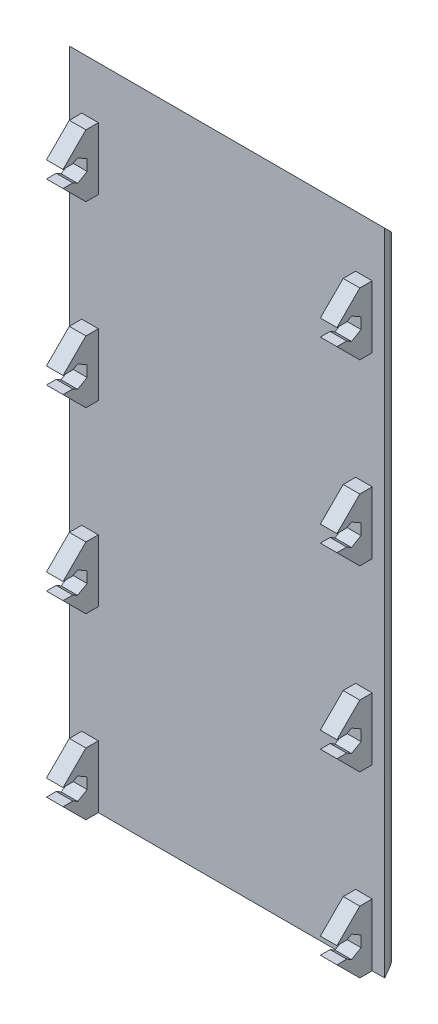
SolidWorks part; units mm, degrees
ref_plane "Front Plane" through (0, 0, 0) normal (0, 0, 1) x (1, 0, 0)
ref_plane "Top Plane" through (0, 0, 0) normal (0, 1, 0) x (1, 0, 0)
ref_plane "Right Plane" through (0, 0, 0) normal (1, 0, 0) x (0, 0, -1)
sketch "Sketch1" plane through (0, 0, 0) normal (0, 1, 0) x (1, 0, 0)
  line L0 (-9.2151, 0) -> (-9.2151, -10)
  line L1 (-9.2151, -10) -> (-5.2151, -10)
  line L2 (-5.2151, -10) -> (-5.2151, 0)
  line L3 (-5.2151, 0) -> (56.7849, 0)
  line L4 (56.7849, 0) -> (56.7849, -10)
  line L5 (56.7849, -10) -> (60.7849, -10)
  line L6 (60.7849, -10) -> (60.7849, 0)
  line L7 (60.7849, 0) -> (63.7849, 0)
  line L8 (-9.2151, 0) -> (-12.2151, 0)
  line L9 (-12.2151, 0) -> (-8.1737, 7)
  line L10 (-8.1737, 7) -> (59.7434, 7)
  line L11 (59.7434, 7) -> (63.7849, 0)
  line L12 (25.7849, 7) -> (25.7849, 0) construction
  dimension "D1" = 3
  dimension "D2" = 10
  dimension "D3" = 70
  dimension "D4" = 7
  dimension "D5" = 4
  dimension "D6" = 60
extrude "Boss-Extrude1" add sketch "Sketch1" along normal blind 156.5
sketch "Sketch4" plane through (60.7849, 0, 0) normal (1, 0, 0) x (0, 0, -1)
  line L0 (0, 156.5) -> (0, 0) construction
  line L1 (-37.5185, 156.5) -> (0, 156.5)
  line L2 (-37.5185, 156.5) -> (-37.5185, 144)
  line L3 (-37.5185, 144) -> (0, 144)
  line L4 (0, 156.5) -> (0, 144)
  line L5 (-37.5185, 156.5) -> (0, 144) construction
  line L6 (-37.5185, 144) -> (0, 156.5) construction
  line L7 (-10, 156.5) -> (0, 156.5) construction
  point P0 (-18.7592, 150.25)
  dimension "D1" = 12.5
extrude "Cut-Extrude1" cut sketch "Sketch4" against normal through all
sketch "Sketch5" plane through (60.7849, 0, 0) normal (1, 0, 0) x (0, 0, -1)
  line L0 (0, 156.5) -> (0, 0) construction
  line L1 (-33.3149, 129) -> (0, 129)
  line L2 (-33.3149, 129) -> (-33.3149, 101)
  line L3 (-33.3149, 101) -> (0, 101)
  line L4 (0, 129) -> (0, 101)
  line L5 (-33.3149, 129) -> (0, 101) construction
  line L6 (-33.3149, 101) -> (0, 129) construction
  line L7 (-10, 144) -> (0, 144) construction
  point P0 (-16.6574, 115)
  dimension "D1" = 28
  dimension "D2" = 15
extrude "Cut-Extrude2" cut sketch "Sketch5" against normal through all
sketch "Sketch6" plane through (0, 0, 0) normal (1, 0, 0) x (0, 0, -1)
  line L0 (-10, 144) -> (-10, 129) construction
  line L1 (-2.7, 137.8279) -> (-5, 139.1558)
  line L2 (-5, 139.1558) -> (-7.3, 137.8279)
  line L3 (-7.3, 137.8279) -> (-7.3, 135.1721)
  line L4 (-7.3, 135.1721) -> (-5, 133.8442)
  line L5 (-5, 133.8442) -> (-2.7, 135.1721)
  line L6 (-2.7, 135.1721) -> (-2.7, 137.8279)
  line L7 (-10, 144) -> (0, 144) construction
  line L8 (-6.15, 138.4919) -> (-10, 138.4919)
  line L9 (-6.15, 134.5081) -> (-10, 134.5081)
  line L10 (-10, 134.5081) -> (-10, 138.4919)
  circle A1 centre (-5, 136.5) radius 2.3 construction
  dimension "D1" = 4.6
  dimension "D2" = 7.5
  dimension "D3" = 5
extrude "Cut-Extrude3" cut sketch "Sketch6" against normal through all and the other way through all contours L10 L9 L4 L3 L2 L8 | L5 L6 L1 L2 L3 L4 region at (0, 136.5, 5) region at (0, 136.5, 8.5351)
pattern_linear "LPattern1" count 4 spacing 43 along (0, -1, 0) of "Cut-Extrude2", "Cut-Extrude3"
chamfer "Chamfer3" distance 7 angle 45 1 edges at (25.7849, 156.5, -7)
fillet "Fillet1" radius 8 2 edges at (-8.1737, 74.75, -7) (59.7434, 74.75, -7)
chamfer "Chamfer5" distance 7 angle 45 16 edges at (58.7849, 43, 10) (58.7849, 144, 10) (58.7849, 129, 10) (-7.2151, 144, 10) (-7.2151, 129, 10) (-7.2151, 101, 10) (-7.2151, 86, 10) (58.7849, 101, 10) (58.7849, 86, 10) (58.7849, 58, 10) (58.7849, 0, 10) (58.7849, 15, 10) (-7.2151, 0, 10) (-7.2151, 15, 10) (-7.2151, 58, 10) (-7.2151, 43, 10)
sketch "Sketch7" plane through (0, 0, -7) normal (0, 0, -1) x (-1, 0, 0)
  line L8 (3.5549, 82.737) -> (-11.316, 82.737) construction
  line L14 (-11.316, 128.6101) -> (-40.2538, 128.6101) construction
  line L20 (-11.316, 128.6101) -> (-11.316, 82.737) construction
  line L22 (-40.2538, 128.6101) -> (-40.2538, 82.737) construction
  line L23 (-11.316, 82.737) -> (-40.2538, 82.737) construction
  line L24 (3.5549, 0) -> (3.5549, 149.5) construction
  line L25 (-11.316, 127.6101) -> (-11.316, 116.1874)
  line L26 (-12.316, 128.6101) -> (-39.2538, 128.6101)
  line L27 (-11.316, 115.6101) -> (-40.2538, 115.6101) construction
  line L28 (-40.2538, 127.6101) -> (-40.2538, 115.6101)
  line L29 (-40.2538, 82.737) -> (-55.1246, 82.737) construction
  line L30 (-55.1246, 149.5) -> (-55.1246, 0) construction
  line L31 (-11.316, 149.5) -> (-11.316, 128.6101) construction
  line L32 (3.5549, 149.5) -> (-55.1246, 149.5) construction
  line L35 (-11.316, 107.5272) -> (-17.816, 103.7744)
  line L38 (-25.316, 99.4443) -> (-39.7538, 91.1086)
  line L39 (-11.316, 107.5272) -> (-11.316, 93.237)
  line L40 (-40.2538, 90.2426) -> (-40.2538, 82.737)
  line L41 (-40.2538, 82.737) -> (-32.316, 87.3199)
  line L42 (-32.316, 87.3199) -> (-32.316, 93.237) construction
  line L43 (-18.316, 102.9084) -> (-18.316, 93.237)
  line L44 (-11.316, 93.237) -> (-32.316, 93.237) construction
  line L45 (-25.316, 99.4443) -> (-25.316, 93.237)
  line L46 (-18.316, 93.237) -> (-25.316, 93.237) construction
  line L47 (-39.7538, 107.2744) -> (-18.566, 119.5072)
  line L48 (-40.2538, 115.6101) -> (-40.2538, 106.9857) construction
  line L49 (-11.316, 82.737) -> (-40.2538, 82.737) construction
  line L50 (-40.2538, 106.4084) -> (-40.2538, 100.5631)
  line L51 (-32.316, 87.3199) -> (-30.9714, 88.0962)
  line L52 (-11.816, 115.3214) -> (-31.566, 103.9187)
  line L53 (-33.2538, 121.1101) -> (-33.2538, 119.3988)
  line L54 (-31.566, 103.0527) -> (-25.316, 99.4443)
  line L55 (-32.316, 95.4028) -> (-39.7538, 99.6971)
  line L56 (-33.5038, 118.9657) -> (-40.2538, 115.0686)
  line L57 (-40.2538, 115.0686) -> (-40.2538, 115.6101)
  line L58 (-32.7538, 121.6101) -> (-18.816, 121.6101)
  line L59 (-18.316, 121.1101) -> (-18.316, 119.9402)
  line L60 (-11.316, 121.6101) -> (-18.316, 121.6101) construction
  line L61 (-33.2538, 121.6101) -> (-40.2538, 121.6101) construction
  line L62 (-40.2538, 128.6101) -> (-11.316, 128.6101) construction
  line L63 (-11.316, 128.6101) -> (-11.316, 82.737) construction
  arc A7 (-11.316, 93.237) -> (-32.316, 93.237) centre (-21.816, 93.237) cw
  arc A8 (-18.316, 93.237) -> (-25.316, 93.237) centre (-21.816, 93.237) cw
  arc A9 (-17.816, 103.7744) -> (-18.316, 102.9084) centre (-17.316, 102.9084) ccw
  arc A10 (-11.816, 115.3214) -> (-11.316, 116.1874) centre (-12.316, 116.1874) ccw
  arc A11 (-11.316, 127.6101) -> (-12.316, 128.6101) centre (-12.316, 127.6101) ccw
  arc A12 (-39.7538, 91.1086) -> (-40.2538, 90.2426) centre (-39.2538, 90.2426) ccw
  arc A13 (-39.2538, 128.6101) -> (-40.2538, 127.6101) centre (-39.2538, 127.6101) ccw
  arc A14 (-40.2538, 106.4084) -> (-39.7538, 107.2744) centre (-39.2538, 106.4084) cw
  arc A15 (-39.7538, 99.6971) -> (-40.2538, 100.5631) centre (-39.2538, 100.5631) cw
  arc A16 (-32.7538, 121.6101) -> (-33.2538, 121.1101) centre (-32.7538, 121.1101) ccw
  arc A17 (-33.5038, 118.9657) -> (-33.2538, 119.3988) centre (-33.7538, 119.3988) ccw
  arc A18 (-18.316, 121.1101) -> (-18.816, 121.6101) centre (-18.816, 121.1101) ccw
  arc A19 (-18.566, 119.5072) -> (-18.316, 119.9402) centre (-18.816, 119.9402) ccw
  arc A20 (-31.566, 103.0527) -> (-31.566, 103.9187) centre (-31.316, 103.4857) cw
  point P59 (-40.2538, 106.9857)
  point P63 (-40.2538, 99.9857)
  dimension "D11" = 7
  dimension "D12" = 30
  dimension "D10" = 7
  dimension "D14" = 0.5
  dimension "D16" = 7
  dimension "D6" = 7
  dimension "D13" = 1
  dimension "D2" = 1
  dimension "0.5" = 1
  dimension "D18" = 1
  dimension "D4" = 0.5
  dimension "D1" = 7
  dimension "D3" = 7
  dimension "D5" = 7
  dimension "D7" = 7
  dimension "D8" = 7
  dimension "D9" = 7
  dimension "D15" = 30
  dimension "D17" = 7
extrude "Cut-Extrude4" cut sketch "Sketch7" against normal blind 1 contours L54 A20 L52 A10 L25 A11 L26 A13 L28 L57 L56 L53 L58 L59 L47 A14 L50 A15 L55 L38 | L38 A12 L40 L41 L51 A7 L39 L35 A9 L43 A8 L45 region at (11.7564, 121.8988, -7) region at (25.697, 96.3406, -7)
sketch "Sketch8" plane through (0, 0, -7) normal (0, 0, -1) x (-1, 0, 0)
  line L0 (-40.2538, 128.6101) -> (-40.2538, 50.6101) construction
  line L1 (-55.1246, 149.5) -> (-55.1246, 0) construction
  line L2 (-25.7849, 128.6101) -> (-55.1246, 128.6101) construction
  line L3 (-12.316, 128.6101) -> (-39.2538, 128.6101) construction
  line L5 (-40.2538, 127.6101) -> (-40.2538, 115.0686) construction
  text T0 "DREam" font "VALORANT" height in points 14
  point P8 (0, 0)
  point P9 (-40.2538, 28.6033)
  point P10 (-40.2538, 16.755)
  point P13 (-40.2538, 32.5011)
  point P15 (-40.2538, 26.3899)
  point P16 (-40.2538, 24.1897)
  dimension "D1" = 78
extrude "Cut-Extrude5" cut sketch "Sketch8" against normal blind 1
fillet "Fillet2" radius 0.5 2 edges at (32.316, 95.4028, -6.5) (25.316, 99.4443, -6.5)
